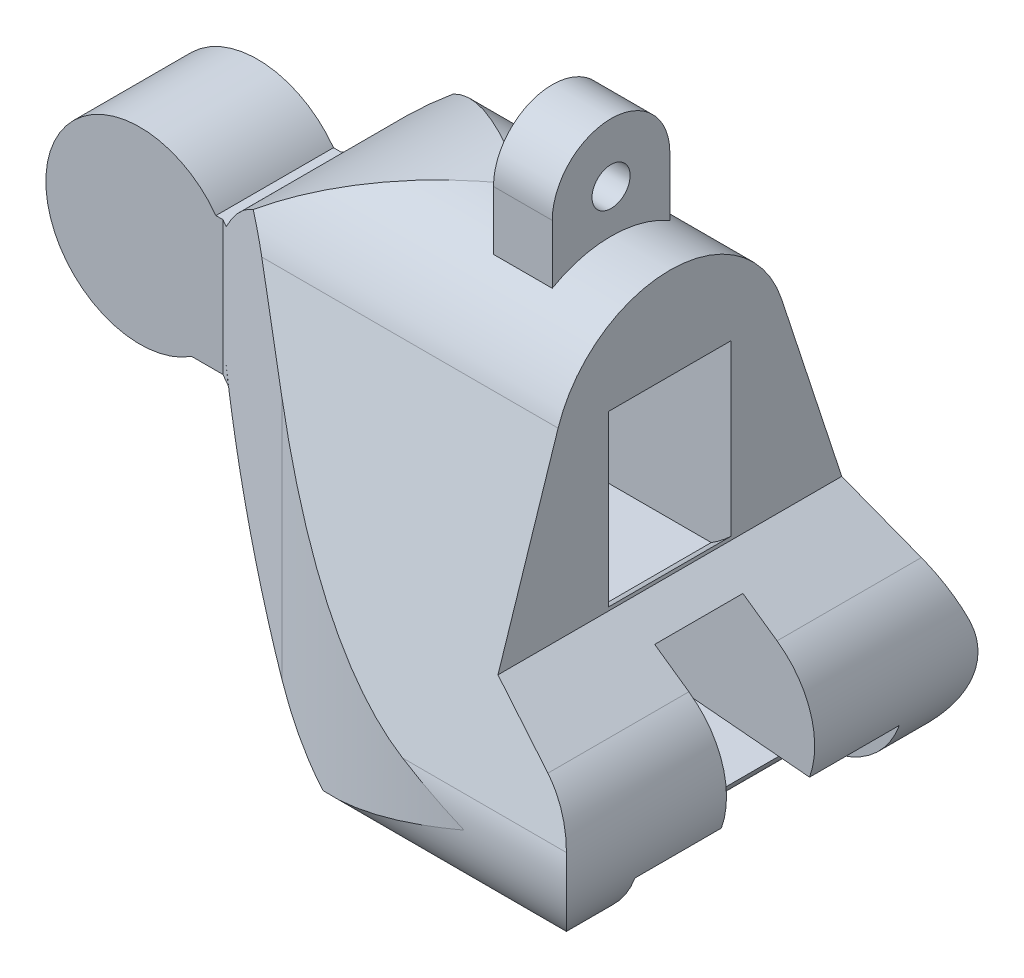
SolidWorks part; units mm, degrees
material "Polycarbonate"
ref_plane "Front Plane" through (0, 0, 0) normal (0, 0, 1) x (1, 0, 0)
ref_plane "Top Plane" through (0, 0, 0) normal (0, 1, 0) x (1, 0, 0)
ref_plane "Right Plane" through (0, 0, 0) normal (1, 0, 0) x (0, 0, -1)
sketch "Sketch2" plane through (0, 0, 0) normal (0, 0, 1) x (1, 0, 0)
  line L0 (4.4873, -2.3813) -> (4.4873, 2.3813)
  arc A0 (4.4873, 2.3813) -> (4.4873, -2.3813) centre (0, 0) ccw
  dimension "D1" = 10.16
  dimension "D2" = 4.7625
extrude "Boss-Extrude1" add sketch "Sketch2" along normal blind 6.35
sketch "Sketch3" plane through (0, 0, 0) normal (0, 0, 1) x (1, 0, 0)
  line L0 (4.4873, -2.3813) -> (4.4873, 2.3813) construction
  line L1 (4.4873, 9.525) -> (25.4423, 9.525)
  line L2 (4.4873, 9.525) -> (4.4873, -15.875)
  line L3 (4.4873, -15.875) -> (25.4423, -15.875)
  line L4 (25.4423, 9.525) -> (25.4423, -4.7625)
  line L5 (4.4873, 9.525) -> (25.4423, -15.875) construction
  line L6 (4.4873, -15.875) -> (25.4423, 9.525) construction
  line L7 (25.4423, -4.7625) -> (41.3126, -15.875)
  line L8 (41.3126, -15.875) -> (25.4423, -15.875)
  point P0 (14.9648, -3.175)
  dimension "D1" = 20.955
  dimension "D2" = 25.4
  dimension "D3" = 9.525
  dimension "D4" = 55
  dimension "D5" = 11.1125
extrude "Boss-Extrude2" add sketch "Sketch3" along normal offset from surface (22.225 mm away) 7.9375 from offset 7.9375 separate body up to face at (-0.2963, 0, 6.35) offset beyond the face yes offset against normal yes
sketch "Sketch4" plane through (0, 9.525, 0) normal (0, 1, 0) x (1, 0, 0)
  line L0 (4.4873, -6.35) -> (11.9942, -10.6841)
  line L1 (4.4873, 0) -> (11.9942, 4.3341)
  line L2 (4.4873, -14.2875) -> (4.4873, 7.9375) construction
  line L4 (25.4423, -14.2875) -> (4.4873, -14.2875) construction
  line L5 (25.4423, 7.9375) -> (4.4873, 7.9375) construction
  line L6 (4.4873, -14.2875) -> (4.4873, -6.35)
  line L7 (25.4423, 7.9375) -> (4.4873, 7.9375)
  line L8 (25.4423, -14.2875) -> (4.4873, -14.2875)
  line L9 (4.4873, 0) -> (4.4873, 7.9375)
  arc A0 (11.9942, -10.6841) -> (25.4423, -14.2875) centre (25.4423, 12.6088) ccw
  arc A1 (11.9942, 4.3341) -> (25.4423, 7.9375) centre (25.4423, -18.9588) cw
  dimension "D1" = 60
  dimension "D2" = 60
extrude "Cut-Extrude1" cut sketch "Sketch4" against normal through all
sketch "Sketch5" plane through (0, 0, 0) normal (0, 0, 1) x (1, 0, 0)
  line L0 (41.3126, -15.875) -> (25.4423, -4.7625) construction
  line L2 (11.9942, -15.875) -> (25.4423, -15.875) construction
  line L3 (22.7376, -15.875) -> (26.2079, -15.875) construction
  line L4 (25.4423, -15.875) -> (41.3126, -15.875) construction
  line L5 (41.3126, -15.875) -> (25.4423, -4.7625) construction
  line L6 (4.4873, -15.875) -> (4.4873, -2.3813)
  line L7 (25.4423, 9.525) -> (17.5048, 9.525) construction
  line L8 (25.4423, 9.525) -> (11.9942, 9.525) construction
  line L10 (4.4873, 2.3813) -> (4.4873, -2.3813) construction
  line L11 (4.4873, 2.3813) -> (4.4873, 9.525)
  line L12 (4.4873, 9.525) -> (17.5048, 9.525)
  line L13 (26.2079, -15.875) -> (41.3126, -15.875)
  line L16 (41.3126, -15.875) -> (28.9396, -7.2113)
  line L17 (4.4873, -2.3813) -> (4.8365, -3.3405)
  line L18 (4.4873, -15.875) -> (22.7376, -15.875)
  arc A1 (17.5048, 9.525) -> (4.4873, 2.3813) centre (17.5048, -5.9073) ccw
  arc A3 (4.8365, -3.3405) -> (22.7376, -15.875) centre (22.7376, 3.175) ccw
  arc A4 (26.2079, -15.875) -> (28.9396, -7.2113) centre (26.2079, -11.1125) ccw
  dimension "D1" = 20
  dimension "D2" = 7.9375
  dimension "D3" = 4.7625
  dimension "D4" = 19.05
extrude "Cut-Extrude2" cut sketch "Sketch5" along normal blind 25.24 from surface contours L18 A4 A3 L17 L6 | A4 A3 L13 L16 | A1 L12 L11 region at (8.6708, -12.2776, 0) region at (7.5722, 7.5055, 0) region at (33.8275, -13.515, 0) starting at face at (30.7324, -12.1708, -7.9375)
sketch "Sketch7" plane through (25.4423, 0, 0) normal (1, 0, 0) x (0, 0, -1)
  line L0 (-3.175, 9.525) -> (-3.175, -7.9375) construction
  line L2 (-9.525, -15.875) -> (3.175, -15.875) construction
  line L3 (3.175, -15.875) -> (7.9375, -15.875)
  line L4 (6.7396, 9.525) -> (-13.0896, 9.525) construction
  line L5 (7.9375, -4.7625) -> (7.9375, 9.525) construction
  line L10 (7.9375, 9.525) -> (-14.2875, 9.525)
  line L11 (7.9375, -4.7625) -> (7.9375, 9.525)
  line L12 (-9.525, -15.875) -> (-14.2875, -15.875)
  line L14 (-14.0509, -9.6301) -> (-9.2096, 5.1515)
  line L15 (7.7009, -9.6301) -> (2.8596, 5.1515)
  line L18 (7.9375, -4.7625) -> (7.9375, -15.875)
  line L19 (7.9375, -15.875) -> (7.9375, -4.7625)
  line L20 (-14.2875, -15.875) -> (-14.2875, 9.525)
  arc A0 (-9.2096, 5.1515) -> (2.8596, 5.1515) centre (-3.175, 3.175) cw
  arc A3 (-14.0509, -9.6301) -> (-9.525, -15.875) centre (-9.525, -11.1125) ccw
  arc A4 (7.7009, -9.6301) -> (3.175, -15.875) centre (3.175, -11.1125) cw
  point P12 (-3.175, 9.525)
  line M3 (-14.2875, 9.525) -> (-14.2875, -4.7625)
  line M5 (7.9375, -4.7625) -> (7.9375, 9.525)
  line M6 (7.9375, 9.525) -> (-14.2875, 9.525)
  line M30 (-14.2875, -4.7625) -> (7.9375, -4.7625)
  dimension "D1" = 6.35
  dimension "D2" = 4.7625
  dimension "D3" = 25.4
  dimension "D4" = 4.7625
extrude "Cut-Extrude7" cut sketch "Sketch7" against normal blind 19.05 and the other way blind 10 contours A3 L20 L12 | L19 A4 L3 region at (25.4423, -14.8112, -6.8737) region at (25.4423, -14.8112, 13.2237)
extrude "Cut-Extrude10" cut sketch "Sketch7<4>" against normal blind 17.78 and the other way blind 10.16 contours L14 A0 L10 M3 M30 | A0 L15 M6 M30 M5 | L15 A4 L18 M30 | A3 L14 L20 M30 region at (25.4423, -6.6478, -7.3305) region at (25.4423, 4.0189, -5.3307) region at (25.4423, 4.0189, 11.6807) region at (25.4423, -6.6478, 13.6805)
sketch "Sketch7<4>" plane through (25.4423, 0, 0) normal (1, 0, 0) x (0, 0, -1) same geometry as "Sketch7"
sketch "Sketch8" plane through (0, 0, 6.35) normal (0, 0, 1) x (1, 0, 0)
  line L0 (25.4423, 4.572) -> (25.4423, -4.572)
  line L2 (17.6953, 5.4005) -> (24.3758, 5.4005)
  line L3 (24.3758, -5.4005) -> (17.6953, -5.4005)
  line L4 (17.6953, 5.4005) -> (17.6953, -5.4005)
  line L5 (25.4423, -4.7625) -> (25.4423, 5.1515) construction
  arc A0 (25.4423, 4.572) -> (24.3758, 5.4005) centre (21.0356, 0) ccw
  arc A1 (25.4423, 4.572) -> (25.4423, -4.572) centre (21.0356, 0) ccw
  arc A2 (24.3758, -5.4005) -> (25.4423, -4.572) centre (21.0356, 0) ccw
  arc A3 (25.4423, 4.572) -> (25.4423, -4.572) centre (21.0356, 0) ccw
  circle A4 centre (21.0356, 0) radius 5.08 construction
  point P12 (17.6953, 0)
  dimension "D1" = 12.7
  dimension "D6" = 10.16
  dimension "D2" = 9.144
  dimension "D3" = 3.3403
extrude "Cut-Extrude8" cut sketch "Sketch8" against normal blind 6.604 from offset 0.127 contours L3 A1 L0 A0 L2 L4 region at (21.5339, 0, 6.35)
sketch "Sketch12" plane through (25.4423, 0, 0) normal (1, 0, 0) x (0, 0, -1)
  line L1 (-6.35, 8.6743) -> (0, 8.6743)
  line L2 (-6.35, 8.6743) -> (-6.35, 11.8493)
  line L4 (0, 8.6743) -> (0, 11.8493)
  arc A0 (2.8596, 5.1515) -> (-9.2096, 5.1515) centre (-3.175, 3.175) ccw construction
  arc A1 (2.8596, 5.1515) -> (-9.2096, 5.1515) centre (-3.175, 3.175) ccw construction
  arc A2 (0, 11.8493) -> (-6.35, 11.8493) centre (-3.175, 11.8493) ccw
  point P8 (-3.175, 8.6743)
  point P9 (-3.175, 9.525)
  dimension "D1" = 6.35
  dimension "D2" = 3.175
extrude "Boss-Extrude3" add sketch "Sketch12" against normal blind 3.175 from offset 3.175 offset against normal yes
hole_wizard "#1 Clearance Hole1" positions "Sketch13" profile "Sketch14" hole size "#1" standard "ANSI Inch" end condition up to next
sketch "Sketch13" plane through (22.2673, 0, 0) normal (1, 0, 0) x (0, 0, -1)
  point P0 (-3.175, 11.8493)
sketch "Sketch14" plane through (22.2673, 11.8493, 3.175) normal (0, 1, 0) x (0, 0, -1)
  line L0 (0, 0) -> (0, 3.176)
  line L1 (0, 3.176) -> (1.0287, 3.176)
  line L2 (1.0287, 3.176) -> (1.0287, 0)
  line L5 (1.0287, 0) -> (0, 0)
  line L11 (0, -6.35) -> (0, 107.95) construction
  dimension "Thru Hole Dia." = 2.0574
  dimension "Thru Hole Depth" = 3.176
ref_plane "Plane1" through (30.9704, 0, 0) normal (1, 0, 0) x (0, 0, -1)
sketch "Sketch15" plane through (30.9704, 0, 0) normal (1, 0, 0) x (0, 0, -1)
  line L1 (-5.6442, -7.2113) -> (-0.8817, -7.2113)
  line L2 (-5.6442, -7.2113) -> (-5.6442, -11.9738)
  line L3 (-5.6442, -11.9738) -> (-0.8817, -11.9738)
  line L4 (-0.8817, -7.2113) -> (-0.8817, -11.9738)
  line L5 (-5.6442, -7.2113) -> (-0.8817, -11.9738) construction
  line L6 (-5.6442, -11.9738) -> (-0.8817, -7.2113) construction
  line L7 (-13.2587, -7.2113) -> (6.9087, -7.2113) construction
  point P0 (-3.2629, -9.5925)
  dimension "D1" = 4.7625
  dimension "D2" = 4.7625
extrude "Cut-Extrude15" cut sketch "Sketch15" against normal up to surface (8.7031 mm away) up to face at (22.2673, 11.8493, 2.1463)
sketch "Sketch16" plane through (22.2673, 0, 0) normal (1, 0, 0) x (0, 0, -1)
  line L4 (-0.8817, -11.9738) -> (-0.8817, -7.2113)
  line L5 (-0.8817, -7.2113) -> (-5.6442, -7.2113)
  line L6 (-5.6442, -7.2113) -> (-5.6442, -11.9738)
  line L7 (-5.6442, -11.9738) -> (-0.8817, -11.9738)
  line L8 (-0.8817, -11.9738) -> (-0.8817, -7.2113)
  line L9 (-0.8817, -7.2113) -> (-5.6442, -7.2113)
  line L10 (-5.6442, -7.2113) -> (-5.6442, -11.9738)
  line L11 (-5.6442, -11.9738) -> (-0.8817, -11.9738)
  dimension "D1" = 0
extrude "Cut-Extrude16" cut sketch "Sketch16" against normal through all from surface starting at face at (19.0923, 11.8493, 2.1463)
hole_wizard "#1 Clearance Hole2" positions "Sketch17" profile "Sketch18" hole size "#1" standard "ANSI Inch" end condition up to next
sketch "Sketch17" plane through (22.2673, 0, 0) normal (1, 0, 0) x (0, 0, -1)
  line L8 (-0.8817, -11.9738) -> (-0.8817, -7.2113)
  line L9 (-0.8817, -7.2113) -> (-5.6442, -7.2113)
  line L10 (-5.6442, -7.2113) -> (-5.6442, -11.9738)
  line L11 (-5.6442, -11.9738) -> (-0.8817, -11.9738)
  line L12 (-0.8817, -11.9738) -> (-0.8817, -7.2113)
  line L13 (-0.8817, -7.2113) -> (-5.6442, -7.2113)
  line L14 (-5.6442, -7.2113) -> (-5.6442, -11.9738)
  line L15 (-5.6442, -11.9738) -> (-0.8817, -11.9738)
  line L16 (-5.6442, -7.2113) -> (-0.8817, -11.9738) construction
  point P0 (-3.2629, -9.5925)
  dimension "D1" = 0
sketch "Sketch18" plane through (22.2673, -9.5925, 3.2629) normal (0, 1, 0) x (0, 0, -1)
  line L0 (0, 0) -> (0, 3.176)
  line L1 (0, 3.176) -> (1.0287, 3.176)
  line L2 (1.0287, 3.176) -> (1.0287, 0)
  line L5 (1.0287, 0) -> (0, 0)
  line L11 (0, -6.35) -> (0, 107.95) construction
  dimension "Thru Hole Dia." = 2.0574
  dimension "Thru Hole Depth" = 3.176
sketch "Sketch19" plane through (0, 0, 0.8817) normal (0, 0, 1) x (1, 0, 0)
  line L0 (19.0923, -11.9738) -> (13.484, -13.4765)
  line L1 (19.0923, -7.2113) -> (6.083, -6.0731)
  line L2 (22.2673, -7.2113) -> (27.0929, -5.9183)
  line L3 (11.187, -11.9738) -> (19.0923, -11.9738)
  line L4 (19.0923, -11.9738) -> (19.0923, -7.2113)
  line L5 (19.0923, -7.2113) -> (6.768, -7.2113)
  line L6 (11.187, -11.9738) -> (19.0923, -11.9738) construction
  line L7 (19.0923, -11.9738) -> (19.0923, -7.2113)
  line L8 (19.0923, -7.2113) -> (6.768, -7.2113) construction
  line L9 (28.9396, -7.2113) -> (25.4423, -4.7625) construction
  line L10 (28.9396, -7.2113) -> (27.0929, -5.9183)
  line L11 (22.2673, -11.9738) -> (30.6941, -12.711)
  line L13 (28.9396, -7.2113) -> (22.2673, -7.2113)
  line L14 (22.2673, -7.2113) -> (22.2673, -11.9738)
  line L15 (22.2673, -11.9738) -> (30.8919, -11.9738)
  line L17 (28.9396, -7.2113) -> (22.2673, -7.2113) construction
  line L18 (22.2673, -7.2113) -> (22.2673, -11.9738)
  line L19 (22.2673, -11.9738) -> (30.8919, -11.9738) construction
  arc A1 (6.768, -7.2113) -> (11.187, -11.9738) centre (22.7376, 3.175) ccw
  arc A6 (4.8365, -3.3405) -> (11.9942, -12.5565) centre (22.7376, 3.175) ccw construction
  arc A7 (6.083, -6.0731) -> (13.484, -13.4765) centre (22.7376, 3.175) ccw
  arc A8 (26.2079, -15.875) -> (30.7338, -9.6301) centre (26.2079, -11.1125) ccw construction
  arc A9 (30.8919, -11.9738) -> (28.9396, -7.2113) centre (26.2079, -11.1125) ccw
  arc A12 (30.6941, -12.711) -> (28.9396, -7.2113) centre (26.2079, -11.1125) ccw
  dimension "D2" = 15
  dimension "D3" = 5
  dimension "D5" = 15
  dimension "D6" = 5
  dimension "D1" = 0
  dimension "D4" = 0
extrude "Cut-Extrude17" cut sketch "Sketch19" along normal up to surface (4.7625 mm away) up to face at (13.9838, -9.64, 5.6442)
sketch "Sketch21" plane through (0, 0, 0) normal (0, 0, -1) x (-1, 0, 0)
  line L0 (-4.8365, -3.3405) -> (-4.4873, -2.3813) construction
  line L1 (-5.1668, -4.2482) -> (-4.4873, -2.3813)
  line L2 (-5.1668, -4.2482) -> (-2.7856, -4.2482)
  line L3 (-4.1043, 2.9935) -> (-4.898, 2.9935)
  line L4 (-4.4873, 2.3813) -> (-4.4873, 2.9935)
  line L5 (-4.4873, -2.3813) -> (-4.4873, -4.2482)
  arc A0 (-4.4873, 2.3813) -> (-8.3449, 6.5125) centre (-17.5048, -5.9073) ccw construction
  arc A1 (-4.4873, -2.3813) -> (-4.4873, 2.3813) centre (0, 0) ccw construction
  arc A2 (-4.4873, 2.3813) -> (-4.898, 2.9935) centre (-17.5048, -5.9073) ccw
  arc A3 (-4.4873, -2.3813) -> (-2.7856, -4.2482) centre (0, 0) ccw
  arc A4 (-4.1043, 2.9935) -> (-4.4873, 2.3813) centre (0, 0) ccw
  dimension "D1" = 2.3812
  dimension "D2" = 0.7937
extrude "Boss-Extrude5" add sketch "Sketch21" along normal up to surface contours A2 L4 L3 | L5 L1 L2 region at (4.7138, -3.6259, 0) region at (4.6231, 2.7912, 0) up to face at (7.8201, -0.564, -1.9242)
extrude "Boss-Extrude6" add sketch "Sketch21<3>" against normal up to surface (6.35 mm away) contours A4 L3 A2 | L1 L2 A3 up to face at (-0.2963, 0, 6.35)
sketch "Sketch21<3>" plane through (0, 0, 0) normal (0, 0, -1) x (-1, 0, 0) same geometry as "Sketch21"
sketch "Sketch22" plane through (0, 0, 6.35) normal (0, 0, 1) x (1, 0, 0)
  line L0 (4.4873, 2.3812) -> (4.5012, 2.9935)
  line L1 (4.1043, 2.9935) -> (4.898, 2.9935) construction
  line L2 (4.5012, 2.9935) -> (4.898, 2.9935)
  line L3 (4.898, 2.9935) -> (4.4873, 2.3812)
  line L4 (4.4873, -2.3812) -> (4.4873, -4.2482)
  line L5 (5.1668, -4.2482) -> (2.7856, -4.2482) construction
  line L6 (4.4873, -4.2482) -> (5.1668, -4.2482)
  line L7 (5.1668, -4.2482) -> (4.4873, -2.3812)
extrude "Boss-Extrude8" add sketch "Sketch22" along normal up to surface (0.2371 mm away) up to face at (7.8201, -0.564, 8.2742)
sketch "Sketch28" plane through (0, 0, 0) normal (0, 0, 1) x (1, 0, 0)
  line L0 (22.2673, -11.9738) -> (30.6941, -12.711) construction
  line L1 (26.2079, -15.875) -> (22.7376, -15.875) construction
  line L2 (29.0309, -12.5655) -> (30.6941, -12.711)
  line L3 (26.2079, -15.875) -> (22.7376, -15.875)
  line L4 (13.484, -13.4765) -> (19.0923, -11.9738) construction
  line L5 (13.484, -13.4765) -> (15.8082, -12.8538)
  line L6 (26.2079, -14.2875) -> (22.7376, -14.2875)
  arc A0 (26.2079, -15.875) -> (30.7338, -9.6301) centre (26.2079, -11.1125) ccw construction
  arc A1 (11.9942, -12.5565) -> (16.1833, -14.712) centre (22.7376, 3.175) ccw construction
  arc A2 (16.1833, -14.712) -> (22.7376, -15.875) centre (22.7376, 3.175) ccw construction
  arc A4 (26.2079, -15.875) -> (30.6941, -12.711) centre (26.2079, -11.1125) ccw
  arc A5 (13.484, -13.4765) -> (16.1833, -14.712) centre (22.7376, 3.175) ccw
  arc A6 (16.1833, -14.712) -> (22.7376, -15.875) centre (22.7376, 3.175) ccw
  arc A7 (15.8082, -12.8538) -> (16.7295, -13.2214) centre (22.7376, 3.175) ccw
  arc A8 (16.7295, -13.2214) -> (22.7376, -14.2875) centre (22.7376, 3.175) ccw
  arc A9 (26.2079, -14.2875) -> (29.0309, -12.5655) centre (26.2079, -11.1125) ccw
  arc A10 (14.2551, -12.0889) -> (16.7295, -13.2214) centre (22.7376, 3.175) ccw construction
  arc A11 (26.2079, -14.2875) -> (29.1987, -12.1782) centre (26.2079, -11.1125) ccw construction
  dimension "D3" = 5
  dimension "D4" = 1.6696
  dimension "D2" = 3.4703
  dimension "D5" = 13.2227
  dimension "D1" = 1.5875
extrude "Cut-Extrude19" cut sketch "Sketch28" against normal blind 3.9688 and the other way blind 10.3187
ref_plane "Plane2" through (0, 0, -7.9375) normal (0, 0, -1) x (-1, 0, 0)
ref_plane "Plane3" through (0, 0, 3.175) normal (0, 0, 1) x (1, 0, 0)
